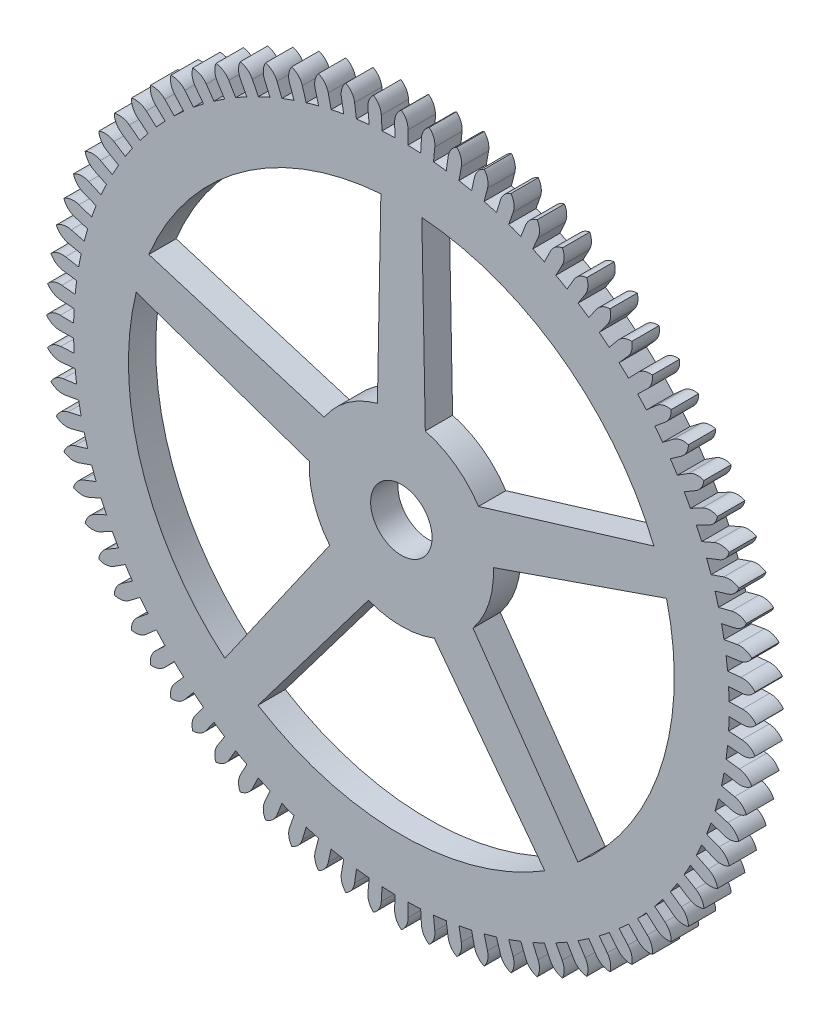
SolidWorks part; units mm, degrees
material "Brass"
ref_plane "Front Plane" through (0, 0, 0) normal (0, 0, 1) x (1, 0, 0)
ref_plane "Top Plane" through (0, 0, 0) normal (0, 1, 0) x (1, 0, 0)
ref_plane "Right Plane" through (0, 0, 0) normal (1, 0, 0) x (0, 0, -1)
sketch "Sketch1" plane through (0, 0, 0) normal (0, 0, 1) x (1, 0, 0)
  line L0 (0, 0) -> (0, 11.4577) construction
  line L1 (-0.1886, 9.6054) -> (-0.1963, 9.9981)
  line L2 (0.1886, 9.6054) -> (0.1963, 9.9981)
  line L3 (0.9417, 9.561) -> (0.9802, 9.9518)
  line L4 (0.5656, 9.5906) -> (0.5887, 9.9827)
  line L5 (1.6889, 9.4577) -> (1.758, 9.8443)
  line L6 (1.3163, 9.5167) -> (1.3701, 9.9057)
  line L7 (2.4258, 9.296) -> (2.5249, 9.676)
  line L8 (2.0589, 9.3841) -> (2.1431, 9.7677)
  line L9 (3.1476, 9.077) -> (3.2763, 9.4481)
  line L10 (2.7888, 9.1936) -> (2.9028, 9.5694)
  line L11 (3.8501, 8.8021) -> (4.0075, 9.1619)
  line L12 (3.5016, 8.9465) -> (3.6447, 9.3122)
  line L13 (4.5289, 8.4729) -> (4.714, 8.8192)
  line L14 (4.1927, 8.6442) -> (4.3641, 8.9975)
  line L15 (5.1797, 8.0914) -> (5.3914, 8.4222)
  line L16 (4.858, 8.2885) -> (5.0566, 8.6273)
  line L17 (5.7985, 7.6601) -> (6.0356, 7.9732)
  line L18 (5.4933, 7.8818) -> (5.7179, 8.204)
  line L19 (6.3817, 7.1815) -> (6.6425, 7.4751)
  line L20 (6.0948, 7.4265) -> (6.3439, 7.7301)
  line L21 (6.9255, 6.6587) -> (7.2085, 6.9309)
  line L22 (6.6587, 6.9255) -> (6.9309, 7.2085)
  line L23 (7.4265, 6.0948) -> (7.7301, 6.3439)
  line L24 (7.1815, 6.3817) -> (7.4751, 6.6425)
  line L25 (7.8818, 5.4933) -> (8.204, 5.7179)
  line L26 (7.6601, 5.7985) -> (7.9732, 6.0356)
  line L27 (8.2885, 4.858) -> (8.6273, 5.0566)
  line L28 (8.0914, 5.1797) -> (8.4222, 5.3914)
  line L29 (8.6442, 4.1927) -> (8.9975, 4.3641)
  line L30 (8.4729, 4.5289) -> (8.8192, 4.714)
  line L31 (8.9465, 3.5016) -> (9.3122, 3.6447)
  line L32 (8.8021, 3.8501) -> (9.1619, 4.0075)
  line L33 (9.1936, 2.7888) -> (9.5694, 2.9028)
  line L34 (9.077, 3.1476) -> (9.4481, 3.2763)
  line L35 (9.3841, 2.0589) -> (9.7677, 2.1431)
  line L36 (9.296, 2.4258) -> (9.676, 2.5249)
  line L37 (9.5167, 1.3163) -> (9.9057, 1.3701)
  line L38 (9.4577, 1.6889) -> (9.8443, 1.758)
  line L39 (9.5906, 0.5656) -> (9.9827, 0.5887)
  line L40 (9.561, 0.9417) -> (9.9518, 0.9802)
  line L41 (9.6054, -0.1886) -> (9.9981, -0.1963)
  line L42 (9.6054, 0.1886) -> (9.9981, 0.1963)
  line L43 (9.561, -0.9417) -> (9.9518, -0.9802)
  line L44 (9.5906, -0.5656) -> (9.9827, -0.5887)
  line L45 (9.4577, -1.6889) -> (9.8443, -1.758)
  line L46 (9.5167, -1.3163) -> (9.9057, -1.3701)
  line L47 (9.296, -2.4258) -> (9.676, -2.5249)
  line L48 (9.3841, -2.0589) -> (9.7677, -2.1431)
  line L49 (9.077, -3.1476) -> (9.4481, -3.2763)
  line L50 (9.1936, -2.7888) -> (9.5694, -2.9028)
  line L51 (8.8021, -3.8501) -> (9.1619, -4.0075)
  line L52 (8.9465, -3.5016) -> (9.3122, -3.6447)
  line L53 (8.4729, -4.5289) -> (8.8192, -4.714)
  line L54 (8.6442, -4.1927) -> (8.9975, -4.3641)
  line L55 (8.0914, -5.1797) -> (8.4222, -5.3914)
  line L56 (8.2885, -4.858) -> (8.6273, -5.0566)
  line L57 (7.6601, -5.7985) -> (7.9732, -6.0356)
  line L58 (7.8818, -5.4933) -> (8.204, -5.7179)
  line L59 (7.1815, -6.3817) -> (7.4751, -6.6425)
  line L60 (7.4265, -6.0948) -> (7.7301, -6.3439)
  line L61 (6.6587, -6.9255) -> (6.9309, -7.2085)
  line L62 (6.9255, -6.6587) -> (7.2085, -6.9309)
  line L63 (6.0948, -7.4265) -> (6.3439, -7.7301)
  line L64 (6.3817, -7.1815) -> (6.6425, -7.4751)
  line L65 (5.4933, -7.8818) -> (5.7179, -8.204)
  line L66 (5.7985, -7.6601) -> (6.0356, -7.9732)
  line L67 (4.858, -8.2885) -> (5.0566, -8.6273)
  line L68 (5.1797, -8.0914) -> (5.3914, -8.4222)
  line L69 (4.1927, -8.6442) -> (4.3641, -8.9975)
  line L70 (4.5289, -8.4729) -> (4.714, -8.8192)
  line L71 (3.5016, -8.9465) -> (3.6447, -9.3122)
  line L72 (3.8501, -8.8021) -> (4.0075, -9.1619)
  line L73 (2.7888, -9.1936) -> (2.9028, -9.5694)
  line L74 (3.1476, -9.077) -> (3.2763, -9.4481)
  line L75 (2.0589, -9.3841) -> (2.1431, -9.7677)
  line L76 (2.4258, -9.296) -> (2.5249, -9.676)
  line L77 (1.3163, -9.5167) -> (1.3701, -9.9057)
  line L78 (1.6889, -9.4577) -> (1.758, -9.8443)
  line L79 (0.5656, -9.5906) -> (0.5887, -9.9827)
  line L80 (0.9417, -9.561) -> (0.9802, -9.9518)
  line L81 (-0.1886, -9.6054) -> (-0.1963, -9.9981)
  line L82 (0.1886, -9.6054) -> (0.1963, -9.9981)
  line L83 (-0.9417, -9.561) -> (-0.9802, -9.9518)
  line L84 (-0.5656, -9.5906) -> (-0.5887, -9.9827)
  line L85 (-1.6889, -9.4577) -> (-1.758, -9.8443)
  line L86 (-1.3163, -9.5167) -> (-1.3701, -9.9057)
  line L87 (-2.4258, -9.296) -> (-2.5249, -9.676)
  line L88 (-2.0589, -9.3841) -> (-2.1431, -9.7677)
  line L89 (-3.1476, -9.077) -> (-3.2763, -9.4481)
  line L90 (-2.7888, -9.1936) -> (-2.9028, -9.5694)
  line L91 (-3.8501, -8.8021) -> (-4.0075, -9.1619)
  line L92 (-3.5016, -8.9465) -> (-3.6447, -9.3122)
  line L93 (-4.5289, -8.4729) -> (-4.714, -8.8192)
  line L94 (-4.1927, -8.6442) -> (-4.3641, -8.9975)
  line L95 (-5.1797, -8.0914) -> (-5.3914, -8.4222)
  line L96 (-4.858, -8.2885) -> (-5.0566, -8.6273)
  line L97 (-5.7985, -7.6601) -> (-6.0356, -7.9732)
  line L98 (-5.4933, -7.8818) -> (-5.7179, -8.204)
  line L99 (-6.3817, -7.1815) -> (-6.6425, -7.4751)
  line L100 (-6.0948, -7.4265) -> (-6.3439, -7.7301)
  line L101 (-6.9255, -6.6587) -> (-7.2085, -6.9309)
  line L102 (-6.6587, -6.9255) -> (-6.9309, -7.2085)
  line L103 (-7.4265, -6.0948) -> (-7.7301, -6.3439)
  line L104 (-7.1815, -6.3817) -> (-7.4751, -6.6425)
  line L105 (-7.8818, -5.4933) -> (-8.204, -5.7179)
  line L106 (-7.6601, -5.7985) -> (-7.9732, -6.0356)
  line L107 (-8.2885, -4.858) -> (-8.6273, -5.0566)
  line L108 (-8.0914, -5.1797) -> (-8.4222, -5.3914)
  line L109 (-8.6442, -4.1927) -> (-8.9975, -4.3641)
  line L110 (-8.4729, -4.5289) -> (-8.8192, -4.714)
  line L111 (-8.9465, -3.5016) -> (-9.3122, -3.6447)
  line L112 (-8.8021, -3.8501) -> (-9.1619, -4.0075)
  line L113 (-9.1936, -2.7888) -> (-9.5694, -2.9028)
  line L114 (-9.077, -3.1476) -> (-9.4481, -3.2763)
  line L115 (-9.3841, -2.0589) -> (-9.7677, -2.1431)
  line L116 (-9.296, -2.4258) -> (-9.676, -2.5249)
  line L117 (-9.5167, -1.3163) -> (-9.9057, -1.3701)
  line L118 (-9.4577, -1.6889) -> (-9.8443, -1.758)
  line L119 (-9.5906, -0.5656) -> (-9.9827, -0.5887)
  line L120 (-9.561, -0.9417) -> (-9.9518, -0.9802)
  line L121 (-9.6054, 0.1886) -> (-9.9981, 0.1963)
  line L122 (-9.6054, -0.1886) -> (-9.9981, -0.1963)
  line L123 (-9.561, 0.9417) -> (-9.9518, 0.9802)
  line L124 (-9.5906, 0.5656) -> (-9.9827, 0.5887)
  line L125 (-9.4577, 1.6889) -> (-9.8443, 1.758)
  line L126 (-9.5167, 1.3163) -> (-9.9057, 1.3701)
  line L127 (-9.296, 2.4258) -> (-9.676, 2.5249)
  line L128 (-9.3841, 2.0589) -> (-9.7677, 2.1431)
  line L129 (-9.077, 3.1476) -> (-9.4481, 3.2763)
  line L130 (-9.1936, 2.7888) -> (-9.5694, 2.9028)
  line L131 (-8.8021, 3.8501) -> (-9.1619, 4.0075)
  line L132 (-8.9465, 3.5016) -> (-9.3122, 3.6447)
  line L133 (-8.4729, 4.5289) -> (-8.8192, 4.714)
  line L134 (-8.6442, 4.1927) -> (-8.9975, 4.3641)
  line L135 (-8.0914, 5.1797) -> (-8.4222, 5.3914)
  line L136 (-8.2885, 4.858) -> (-8.6273, 5.0566)
  line L137 (-7.6601, 5.7985) -> (-7.9732, 6.0356)
  line L138 (-7.8818, 5.4933) -> (-8.204, 5.7179)
  line L139 (-7.1815, 6.3817) -> (-7.4751, 6.6425)
  line L140 (-7.4265, 6.0948) -> (-7.7301, 6.3439)
  line L141 (-6.6587, 6.9255) -> (-6.9309, 7.2085)
  line L142 (-6.9255, 6.6587) -> (-7.2085, 6.9309)
  line L143 (-6.0948, 7.4265) -> (-6.3439, 7.7301)
  line L144 (-6.3817, 7.1815) -> (-6.6425, 7.4751)
  line L145 (-5.4933, 7.8818) -> (-5.7179, 8.204)
  line L146 (-5.7985, 7.6601) -> (-6.0356, 7.9732)
  line L147 (-4.858, 8.2885) -> (-5.0566, 8.6273)
  line L148 (-5.1797, 8.0914) -> (-5.3914, 8.4222)
  line L149 (-4.1927, 8.6442) -> (-4.3641, 8.9975)
  line L150 (-4.5289, 8.4729) -> (-4.714, 8.8192)
  line L151 (-3.5016, 8.9465) -> (-3.6447, 9.3122)
  line L152 (-3.8501, 8.8021) -> (-4.0075, 9.1619)
  line L153 (-2.7888, 9.1936) -> (-2.9028, 9.5694)
  line L154 (-3.1476, 9.077) -> (-3.2763, 9.4481)
  line L155 (-2.0589, 9.3841) -> (-2.1431, 9.7677)
  line L156 (-2.4258, 9.296) -> (-2.5249, 9.676)
  line L157 (-1.3163, 9.5167) -> (-1.3701, 9.9057)
  line L158 (-1.6889, 9.4577) -> (-1.758, 9.8443)
  line L159 (-0.5656, 9.5906) -> (-0.5887, 9.9827)
  line L160 (-0.9417, 9.561) -> (-0.9802, 9.9518)
  line L161 (-0.6, 8) -> (-0.7018, 2.6072)
  line L162 (0.6, 8) -> (0.7018, 2.6072)
  line L163 (7.423, 3.0428) -> (2.2628, 1.4731)
  line L164 (7.7939, 1.9015) -> (2.6965, 0.1383)
  line L165 (5.1877, -6.1195) -> (2.1002, -1.6968)
  line L166 (4.2169, -6.8248) -> (0.9648, -2.5218)
  line L167 (-4.2169, -6.8248) -> (-0.9648, -2.5218)
  line L168 (-5.1877, -6.1195) -> (-2.1002, -1.6968)
  line L169 (-7.7939, 1.9015) -> (-2.6965, 0.1383)
  line L170 (-7.423, 3.0428) -> (-2.2628, 1.4731)
  arc A0 (0.5656, 9.5906) -> (0.1886, 9.6054) centre (0, 0) ccw
  arc A1 (-0.1886, 9.6054) -> (-0.5656, 9.5906) centre (0, 0) ccw
  arc A2 (1.3163, 9.5167) -> (0.9417, 9.561) centre (0, 0) ccw
  arc A3 (-0.1963, 9.9981) -> (0, 10.4017) centre (0.2968, 10.0078) cw
  arc A4 (0.1963, 9.9981) -> (0, 10.4017) centre (-0.2968, 10.0078) ccw
  arc A5 (0.5887, 9.9827) -> (0.8161, 10.3696) centre (1.0811, 9.9536) cw
  arc A6 (0.9802, 9.9518) -> (0.8161, 10.3696) centre (0.4893, 10.0002) ccw
  arc A7 (1.3701, 9.9057) -> (1.6272, 10.2736) centre (1.8587, 9.8381) cw
  arc A8 (1.758, 9.8443) -> (1.6272, 10.2736) centre (1.2724, 9.931) ccw
  arc A9 (2.1431, 9.7677) -> (2.4282, 10.1143) centre (2.6249, 9.662) cw
  arc A10 (2.5249, 9.676) -> (2.4282, 10.1143) centre (2.0477, 9.8005) ccw
  arc A11 (2.9028, 9.5694) -> (3.2143, 9.8926) centre (3.3748, 9.4262) cw
  arc A12 (3.2763, 9.4481) -> (3.2143, 9.8926) centre (2.8103, 9.6097) ccw
  arc A13 (3.6447, 9.3122) -> (3.9806, 9.6099) centre (4.104, 9.1324) cw
  arc A14 (4.0075, 9.1619) -> (3.9806, 9.6099) centre (3.5556, 9.3595) ccw
  arc A15 (4.3641, 8.9975) -> (4.7223, 9.268) centre (4.8079, 8.7822) cw
  arc A16 (4.714, 8.8192) -> (4.7223, 9.268) centre (4.279, 9.0517) ccw
  arc A17 (5.0566, 8.6273) -> (5.4349, 8.8689) centre (5.4821, 8.3779) cw
  arc A18 (5.3914, 8.4222) -> (5.4349, 8.8689) centre (4.976, 8.6881) ccw
  arc A19 (5.7179, 8.204) -> (6.114, 8.4152) centre (6.1225, 7.922) cw
  arc A20 (6.0356, 7.9732) -> (6.114, 8.4152) centre (5.6423, 8.2709) ccw
  arc A21 (6.3439, 7.7301) -> (6.7554, 7.9095) centre (6.7252, 7.4172) cw
  arc A22 (6.6425, 7.4751) -> (6.7554, 7.9095) centre (6.2738, 7.8027) ccw
  arc A23 (6.9309, 7.2085) -> (7.3551, 7.3551) centre (7.2864, 6.8667) cw
  arc A24 (7.2085, 6.9309) -> (7.3551, 7.3551) centre (6.8667, 7.2864) ccw
  arc A25 (7.4751, 6.6425) -> (7.9095, 6.7554) centre (7.8027, 6.2738) cw
  arc A26 (7.7301, 6.3439) -> (7.9095, 6.7554) centre (7.4172, 6.7252) ccw
  arc A27 (7.9732, 6.0356) -> (8.4152, 6.114) centre (8.2709, 5.6423) cw
  arc A28 (8.204, 5.7179) -> (8.4152, 6.114) centre (7.922, 6.1225) ccw
  arc A29 (8.4222, 5.3914) -> (8.8689, 5.4349) centre (8.6881, 4.976) cw
  arc A30 (8.6273, 5.0566) -> (8.8689, 5.4349) centre (8.3779, 5.4821) ccw
  arc A31 (8.8192, 4.714) -> (9.268, 4.7223) centre (9.0517, 4.279) cw
  arc A32 (8.9975, 4.3641) -> (9.268, 4.7223) centre (8.7822, 4.8079) ccw
  arc A33 (9.1619, 4.0075) -> (9.6099, 3.9806) centre (9.3595, 3.5556) cw
  arc A34 (9.3122, 3.6447) -> (9.6099, 3.9806) centre (9.1324, 4.104) ccw
  arc A35 (9.4481, 3.2763) -> (9.8926, 3.2143) centre (9.6097, 2.8103) cw
  arc A36 (9.5694, 2.9028) -> (9.8926, 3.2143) centre (9.4262, 3.3748) ccw
  arc A37 (9.676, 2.5249) -> (10.1143, 2.4282) centre (9.8005, 2.0477) cw
  arc A38 (9.7677, 2.1431) -> (10.1143, 2.4282) centre (9.662, 2.6249) ccw
  arc A39 (9.8443, 1.758) -> (10.2736, 1.6272) centre (9.931, 1.2724) cw
  arc A40 (9.9057, 1.3701) -> (10.2736, 1.6272) centre (9.8381, 1.8587) ccw
  arc A41 (9.9518, 0.9802) -> (10.3696, 0.8161) centre (10.0002, 0.4893) cw
  arc A42 (9.9827, 0.5887) -> (10.3696, 0.8161) centre (9.9536, 1.0811) ccw
  arc A43 (9.9981, 0.1963) -> (10.4017, 0) centre (10.0078, -0.2968) cw
  arc A44 (9.9981, -0.1963) -> (10.4017, 0) centre (10.0078, 0.2968) ccw
  arc A45 (9.9827, -0.5887) -> (10.3696, -0.8161) centre (9.9536, -1.0811) cw
  arc A46 (9.9518, -0.9802) -> (10.3696, -0.8161) centre (10.0002, -0.4893) ccw
  arc A47 (9.9057, -1.3701) -> (10.2736, -1.6272) centre (9.8381, -1.8587) cw
  arc A48 (9.8443, -1.758) -> (10.2736, -1.6272) centre (9.931, -1.2724) ccw
  arc A49 (9.7677, -2.1431) -> (10.1143, -2.4282) centre (9.662, -2.6249) cw
  arc A50 (9.676, -2.5249) -> (10.1143, -2.4282) centre (9.8005, -2.0477) ccw
  arc A51 (9.5694, -2.9028) -> (9.8926, -3.2143) centre (9.4262, -3.3748) cw
  arc A52 (9.4481, -3.2763) -> (9.8926, -3.2143) centre (9.6097, -2.8103) ccw
  arc A53 (9.3122, -3.6447) -> (9.6099, -3.9806) centre (9.1324, -4.104) cw
  arc A54 (9.1619, -4.0075) -> (9.6099, -3.9806) centre (9.3595, -3.5556) ccw
  arc A55 (8.9975, -4.3641) -> (9.268, -4.7223) centre (8.7822, -4.8079) cw
  arc A56 (8.8192, -4.714) -> (9.268, -4.7223) centre (9.0517, -4.279) ccw
  arc A57 (8.6273, -5.0566) -> (8.8689, -5.4349) centre (8.3779, -5.4821) cw
  arc A58 (8.4222, -5.3914) -> (8.8689, -5.4349) centre (8.6881, -4.976) ccw
  arc A59 (8.204, -5.7179) -> (8.4152, -6.114) centre (7.922, -6.1225) cw
  arc A60 (7.9732, -6.0356) -> (8.4152, -6.114) centre (8.2709, -5.6423) ccw
  arc A61 (7.7301, -6.3439) -> (7.9095, -6.7554) centre (7.4172, -6.7252) cw
  arc A62 (7.4751, -6.6425) -> (7.9095, -6.7554) centre (7.8027, -6.2738) ccw
  arc A63 (7.2085, -6.9309) -> (7.3551, -7.3551) centre (6.8667, -7.2864) cw
  arc A64 (6.9309, -7.2085) -> (7.3551, -7.3551) centre (7.2864, -6.8667) ccw
  arc A65 (6.6425, -7.4751) -> (6.7554, -7.9095) centre (6.2738, -7.8027) cw
  arc A66 (6.3439, -7.7301) -> (6.7554, -7.9095) centre (6.7252, -7.4172) ccw
  arc A67 (6.0356, -7.9732) -> (6.114, -8.4152) centre (5.6423, -8.2709) cw
  arc A68 (5.7179, -8.204) -> (6.114, -8.4152) centre (6.1225, -7.922) ccw
  arc A69 (5.3914, -8.4222) -> (5.4349, -8.8689) centre (4.976, -8.6881) cw
  arc A70 (5.0566, -8.6273) -> (5.4349, -8.8689) centre (5.4821, -8.3779) ccw
  arc A71 (4.714, -8.8192) -> (4.7223, -9.268) centre (4.279, -9.0517) cw
  arc A72 (4.3641, -8.9975) -> (4.7223, -9.268) centre (4.8079, -8.7822) ccw
  arc A73 (4.0075, -9.1619) -> (3.9806, -9.6099) centre (3.5556, -9.3595) cw
  arc A74 (3.6447, -9.3122) -> (3.9806, -9.6099) centre (4.104, -9.1324) ccw
  arc A75 (3.2763, -9.4481) -> (3.2143, -9.8926) centre (2.8103, -9.6097) cw
  arc A76 (2.9028, -9.5694) -> (3.2143, -9.8926) centre (3.3748, -9.4262) ccw
  arc A77 (2.5249, -9.676) -> (2.4282, -10.1143) centre (2.0477, -9.8005) cw
  arc A78 (2.1431, -9.7677) -> (2.4282, -10.1143) centre (2.6249, -9.662) ccw
  arc A79 (1.758, -9.8443) -> (1.6272, -10.2736) centre (1.2724, -9.931) cw
  arc A80 (1.3701, -9.9057) -> (1.6272, -10.2736) centre (1.8587, -9.8381) ccw
  arc A81 (0.9802, -9.9518) -> (0.8161, -10.3696) centre (0.4893, -10.0002) cw
  arc A82 (0.5887, -9.9827) -> (0.8161, -10.3696) centre (1.0811, -9.9536) ccw
  arc A83 (0.1963, -9.9981) -> (0, -10.4017) centre (-0.2968, -10.0078) cw
  arc A84 (-0.1963, -9.9981) -> (0, -10.4017) centre (0.2968, -10.0078) ccw
  arc A85 (-0.5887, -9.9827) -> (-0.8161, -10.3696) centre (-1.0811, -9.9536) cw
  arc A86 (-0.9802, -9.9518) -> (-0.8161, -10.3696) centre (-0.4893, -10.0002) ccw
  arc A87 (-1.3701, -9.9057) -> (-1.6272, -10.2736) centre (-1.8587, -9.8381) cw
  arc A88 (-1.758, -9.8443) -> (-1.6272, -10.2736) centre (-1.2724, -9.931) ccw
  arc A89 (-2.1431, -9.7677) -> (-2.4282, -10.1143) centre (-2.6249, -9.662) cw
  arc A90 (-2.5249, -9.676) -> (-2.4282, -10.1143) centre (-2.0477, -9.8005) ccw
  arc A91 (-2.9028, -9.5694) -> (-3.2143, -9.8926) centre (-3.3748, -9.4262) cw
  arc A92 (-3.2763, -9.4481) -> (-3.2143, -9.8926) centre (-2.8103, -9.6097) ccw
  arc A93 (-3.6447, -9.3122) -> (-3.9806, -9.6099) centre (-4.104, -9.1324) cw
  arc A94 (-4.0075, -9.1619) -> (-3.9806, -9.6099) centre (-3.5556, -9.3595) ccw
  arc A95 (-4.3641, -8.9975) -> (-4.7223, -9.268) centre (-4.8079, -8.7822) cw
  arc A96 (-4.714, -8.8192) -> (-4.7223, -9.268) centre (-4.279, -9.0517) ccw
  arc A97 (-5.0566, -8.6273) -> (-5.4349, -8.8689) centre (-5.4821, -8.3779) cw
  arc A98 (-5.3914, -8.4222) -> (-5.4349, -8.8689) centre (-4.976, -8.6881) ccw
  arc A99 (-5.7179, -8.204) -> (-6.114, -8.4152) centre (-6.1225, -7.922) cw
  arc A100 (-6.0356, -7.9732) -> (-6.114, -8.4152) centre (-5.6423, -8.2709) ccw
  arc A101 (-6.3439, -7.7301) -> (-6.7554, -7.9095) centre (-6.7252, -7.4172) cw
  arc A102 (-6.6425, -7.4751) -> (-6.7554, -7.9095) centre (-6.2738, -7.8027) ccw
  arc A103 (-6.9309, -7.2085) -> (-7.3551, -7.3551) centre (-7.2864, -6.8667) cw
  arc A104 (-7.2085, -6.9309) -> (-7.3551, -7.3551) centre (-6.8667, -7.2864) ccw
  arc A105 (-7.4751, -6.6425) -> (-7.9095, -6.7554) centre (-7.8027, -6.2738) cw
  arc A106 (-7.7301, -6.3439) -> (-7.9095, -6.7554) centre (-7.4172, -6.7252) ccw
  arc A107 (-7.9732, -6.0356) -> (-8.4152, -6.114) centre (-8.2709, -5.6423) cw
  arc A108 (-8.204, -5.7179) -> (-8.4152, -6.114) centre (-7.922, -6.1225) ccw
  arc A109 (-8.4222, -5.3914) -> (-8.8689, -5.4349) centre (-8.6881, -4.976) cw
  arc A110 (-8.6273, -5.0566) -> (-8.8689, -5.4349) centre (-8.3779, -5.4821) ccw
  arc A111 (-8.8192, -4.714) -> (-9.268, -4.7223) centre (-9.0517, -4.279) cw
  arc A112 (-8.9975, -4.3641) -> (-9.268, -4.7223) centre (-8.7822, -4.8079) ccw
  arc A113 (-9.1619, -4.0075) -> (-9.6099, -3.9806) centre (-9.3595, -3.5556) cw
  arc A114 (-9.3122, -3.6447) -> (-9.6099, -3.9806) centre (-9.1324, -4.104) ccw
  arc A115 (-9.4481, -3.2763) -> (-9.8926, -3.2143) centre (-9.6097, -2.8103) cw
  arc A116 (-9.5694, -2.9028) -> (-9.8926, -3.2143) centre (-9.4262, -3.3748) ccw
  arc A117 (-9.676, -2.5249) -> (-10.1143, -2.4282) centre (-9.8005, -2.0477) cw
  arc A118 (-9.7677, -2.1431) -> (-10.1143, -2.4282) centre (-9.662, -2.6249) ccw
  arc A119 (-9.8443, -1.758) -> (-10.2736, -1.6272) centre (-9.931, -1.2724) cw
  arc A120 (-9.9057, -1.3701) -> (-10.2736, -1.6272) centre (-9.8381, -1.8587) ccw
  arc A121 (-9.9518, -0.9802) -> (-10.3696, -0.8161) centre (-10.0002, -0.4893) cw
  arc A122 (-9.9827, -0.5887) -> (-10.3696, -0.8161) centre (-9.9536, -1.0811) ccw
  arc A123 (-9.9981, -0.1963) -> (-10.4017, 0) centre (-10.0078, 0.2968) cw
  arc A124 (-9.9981, 0.1963) -> (-10.4017, 0) centre (-10.0078, -0.2968) ccw
  arc A125 (-9.9827, 0.5887) -> (-10.3696, 0.8161) centre (-9.9536, 1.0811) cw
  arc A126 (-9.9518, 0.9802) -> (-10.3696, 0.8161) centre (-10.0002, 0.4893) ccw
  arc A127 (-9.9057, 1.3701) -> (-10.2736, 1.6272) centre (-9.8381, 1.8587) cw
  arc A128 (-9.8443, 1.758) -> (-10.2736, 1.6272) centre (-9.931, 1.2724) ccw
  arc A129 (-9.7677, 2.1431) -> (-10.1143, 2.4282) centre (-9.662, 2.6249) cw
  arc A130 (-9.676, 2.5249) -> (-10.1143, 2.4282) centre (-9.8005, 2.0477) ccw
  arc A131 (-9.5694, 2.9028) -> (-9.8926, 3.2143) centre (-9.4262, 3.3748) cw
  arc A132 (-9.4481, 3.2763) -> (-9.8926, 3.2143) centre (-9.6097, 2.8103) ccw
  arc A133 (-9.3122, 3.6447) -> (-9.6099, 3.9806) centre (-9.1324, 4.104) cw
  arc A134 (-9.1619, 4.0075) -> (-9.6099, 3.9806) centre (-9.3595, 3.5556) ccw
  arc A135 (-8.9975, 4.3641) -> (-9.268, 4.7223) centre (-8.7822, 4.8079) cw
  arc A136 (-8.8192, 4.714) -> (-9.268, 4.7223) centre (-9.0517, 4.279) ccw
  arc A137 (-8.6273, 5.0566) -> (-8.8689, 5.4349) centre (-8.3779, 5.4821) cw
  arc A138 (-8.4222, 5.3914) -> (-8.8689, 5.4349) centre (-8.6881, 4.976) ccw
  arc A139 (-8.204, 5.7179) -> (-8.4152, 6.114) centre (-7.922, 6.1225) cw
  arc A140 (-7.9732, 6.0356) -> (-8.4152, 6.114) centre (-8.2709, 5.6423) ccw
  arc A141 (-7.7301, 6.3439) -> (-7.9095, 6.7554) centre (-7.4172, 6.7252) cw
  arc A142 (-7.4751, 6.6425) -> (-7.9095, 6.7554) centre (-7.8027, 6.2738) ccw
  arc A143 (-7.2085, 6.9309) -> (-7.3551, 7.3551) centre (-6.8667, 7.2864) cw
  arc A144 (-6.9309, 7.2085) -> (-7.3551, 7.3551) centre (-7.2864, 6.8667) ccw
  arc A145 (-6.6425, 7.4751) -> (-6.7554, 7.9095) centre (-6.2738, 7.8027) cw
  arc A146 (-6.3439, 7.7301) -> (-6.7554, 7.9095) centre (-6.7252, 7.4172) ccw
  arc A147 (-6.0356, 7.9732) -> (-6.114, 8.4152) centre (-5.6423, 8.2709) cw
  arc A148 (-5.7179, 8.204) -> (-6.114, 8.4152) centre (-6.1225, 7.922) ccw
  arc A149 (-5.3914, 8.4222) -> (-5.4349, 8.8689) centre (-4.976, 8.6881) cw
  arc A150 (-5.0566, 8.6273) -> (-5.4349, 8.8689) centre (-5.4821, 8.3779) ccw
  arc A151 (-4.714, 8.8192) -> (-4.7223, 9.268) centre (-4.279, 9.0517) cw
  arc A152 (-4.3641, 8.9975) -> (-4.7223, 9.268) centre (-4.8079, 8.7822) ccw
  arc A153 (-4.0075, 9.1619) -> (-3.9806, 9.6099) centre (-3.5556, 9.3595) cw
  arc A154 (-3.6447, 9.3122) -> (-3.9806, 9.6099) centre (-4.104, 9.1324) ccw
  arc A155 (-3.2763, 9.4481) -> (-3.2143, 9.8926) centre (-2.8103, 9.6097) cw
  arc A156 (-2.9028, 9.5694) -> (-3.2143, 9.8926) centre (-3.3748, 9.4262) ccw
  arc A157 (-2.5249, 9.676) -> (-2.4282, 10.1143) centre (-2.0477, 9.8005) cw
  arc A158 (-2.1431, 9.7677) -> (-2.4282, 10.1143) centre (-2.6249, 9.662) ccw
  arc A159 (-1.758, 9.8443) -> (-1.6272, 10.2736) centre (-1.2724, 9.931) cw
  arc A160 (-1.3701, 9.9057) -> (-1.6272, 10.2736) centre (-1.8587, 9.8381) ccw
  arc A161 (-0.9802, 9.9518) -> (-0.8161, 10.3696) centre (-0.4893, 10.0002) cw
  arc A162 (-0.5887, 9.9827) -> (-0.8161, 10.3696) centre (-1.0811, 9.9536) ccw
  arc A163 (2.0589, 9.3841) -> (1.6889, 9.4577) centre (0, 0) ccw
  arc A164 (2.7888, 9.1936) -> (2.4258, 9.296) centre (0, 0) ccw
  arc A165 (3.5016, 8.9465) -> (3.1476, 9.077) centre (0, 0) ccw
  arc A166 (4.1927, 8.6442) -> (3.8501, 8.8021) centre (0, 0) ccw
  arc A167 (4.858, 8.2885) -> (4.5289, 8.4729) centre (0, 0) ccw
  arc A168 (5.4933, 7.8818) -> (5.1797, 8.0914) centre (0, 0) ccw
  arc A169 (6.0948, 7.4265) -> (5.7985, 7.6601) centre (0, 0) ccw
  arc A170 (-0.9417, 9.561) -> (-1.3163, 9.5167) centre (0, 0) ccw
  arc A171 (-1.6889, 9.4577) -> (-2.0589, 9.3841) centre (0, 0) ccw
  arc A172 (-2.4258, 9.296) -> (-2.7888, 9.1936) centre (0, 0) ccw
  arc A173 (-3.1476, 9.077) -> (-3.5016, 8.9465) centre (0, 0) ccw
  arc A174 (-3.8501, 8.8021) -> (-4.1927, 8.6442) centre (0, 0) ccw
  arc A175 (-4.5289, 8.4729) -> (-4.858, 8.2885) centre (0, 0) ccw
  arc A176 (-5.1797, 8.0914) -> (-5.4933, 7.8818) centre (0, 0) ccw
  arc A177 (-5.7985, 7.6601) -> (-6.0948, 7.4265) centre (0, 0) ccw
  arc A178 (-6.3817, 7.1815) -> (-6.6587, 6.9255) centre (0, 0) ccw
  arc A179 (-6.9255, 6.6587) -> (-7.1815, 6.3817) centre (0, 0) ccw
  arc A180 (-7.4265, 6.0948) -> (-7.6601, 5.7985) centre (0, 0) ccw
  arc A181 (-7.8818, 5.4933) -> (-8.0914, 5.1797) centre (0, 0) ccw
  arc A182 (-8.2885, 4.858) -> (-8.4729, 4.5289) centre (0, 0) ccw
  arc A183 (-8.6442, 4.1927) -> (-8.8021, 3.8501) centre (0, 0) ccw
  arc A184 (-8.9465, 3.5016) -> (-9.077, 3.1476) centre (0, 0) ccw
  arc A185 (-9.1936, 2.7888) -> (-9.296, 2.4258) centre (0, 0) ccw
  arc A186 (-9.3841, 2.0589) -> (-9.4577, 1.6889) centre (0, 0) ccw
  arc A187 (-9.5167, 1.3163) -> (-9.561, 0.9417) centre (0, 0) ccw
  arc A188 (-9.5906, 0.5656) -> (-9.6054, 0.1886) centre (0, 0) ccw
  arc A189 (-9.6054, -0.1886) -> (-9.5906, -0.5656) centre (0, 0) ccw
  arc A190 (-9.561, -0.9417) -> (-9.5167, -1.3163) centre (0, 0) ccw
  arc A191 (-9.4577, -1.6889) -> (-9.3841, -2.0589) centre (0, 0) ccw
  arc A192 (-9.296, -2.4258) -> (-9.1936, -2.7888) centre (0, 0) ccw
  arc A193 (-9.077, -3.1476) -> (-8.9465, -3.5016) centre (0, 0) ccw
  arc A194 (-8.8021, -3.8501) -> (-8.6442, -4.1927) centre (0, 0) ccw
  arc A195 (-8.4729, -4.5289) -> (-8.2885, -4.858) centre (0, 0) ccw
  arc A196 (-8.0914, -5.1797) -> (-7.8818, -5.4933) centre (0, 0) ccw
  arc A197 (-7.6601, -5.7985) -> (-7.4265, -6.0948) centre (0, 0) ccw
  arc A198 (-7.1815, -6.3817) -> (-6.9255, -6.6587) centre (0, 0) ccw
  arc A199 (-6.6587, -6.9255) -> (-6.3817, -7.1815) centre (0, 0) ccw
  arc A200 (-6.0948, -7.4265) -> (-5.7985, -7.6601) centre (0, 0) ccw
  arc A201 (-5.4933, -7.8818) -> (-5.1797, -8.0914) centre (0, 0) ccw
  arc A202 (-4.858, -8.2885) -> (-4.5289, -8.4729) centre (0, 0) ccw
  arc A203 (-4.1927, -8.6442) -> (-3.8501, -8.8021) centre (0, 0) ccw
  arc A204 (-3.5016, -8.9465) -> (-3.1476, -9.077) centre (0, 0) ccw
  arc A205 (-2.7888, -9.1936) -> (-2.4258, -9.296) centre (0, 0) ccw
  arc A206 (-2.0589, -9.3841) -> (-1.6889, -9.4577) centre (0, 0) ccw
  arc A207 (-1.3163, -9.5167) -> (-0.9417, -9.561) centre (0, 0) ccw
  arc A208 (-0.5656, -9.5906) -> (-0.1886, -9.6054) centre (0, 0) ccw
  arc A209 (0.1886, -9.6054) -> (0.5656, -9.5906) centre (0, 0) ccw
  arc A210 (0.9417, -9.561) -> (1.3163, -9.5167) centre (0, 0) ccw
  arc A211 (1.6889, -9.4577) -> (2.0589, -9.3841) centre (0, 0) ccw
  arc A212 (2.4258, -9.296) -> (2.7888, -9.1936) centre (0, 0) ccw
  arc A213 (3.1476, -9.077) -> (3.5016, -8.9465) centre (0, 0) ccw
  arc A214 (3.8501, -8.8021) -> (4.1927, -8.6442) centre (0, 0) ccw
  arc A215 (4.5289, -8.4729) -> (4.858, -8.2885) centre (0, 0) ccw
  arc A216 (5.1797, -8.0914) -> (5.4933, -7.8818) centre (0, 0) ccw
  arc A217 (5.7985, -7.6601) -> (6.0948, -7.4265) centre (0, 0) ccw
  arc A218 (6.3817, -7.1815) -> (6.6587, -6.9255) centre (0, 0) ccw
  arc A219 (6.9255, -6.6587) -> (7.1815, -6.3817) centre (0, 0) ccw
  arc A220 (7.4265, -6.0948) -> (7.6601, -5.7985) centre (0, 0) ccw
  arc A221 (7.8818, -5.4933) -> (8.0914, -5.1797) centre (0, 0) ccw
  arc A222 (8.2885, -4.858) -> (8.4729, -4.5289) centre (0, 0) ccw
  arc A223 (8.6442, -4.1927) -> (8.8021, -3.8501) centre (0, 0) ccw
  arc A224 (8.9465, -3.5016) -> (9.077, -3.1476) centre (0, 0) ccw
  arc A225 (9.1936, -2.7888) -> (9.296, -2.4258) centre (0, 0) ccw
  arc A226 (9.3841, -2.0589) -> (9.4577, -1.6889) centre (0, 0) ccw
  arc A227 (9.5167, -1.3163) -> (9.561, -0.9417) centre (0, 0) ccw
  arc A228 (9.5906, -0.5656) -> (9.6054, -0.1886) centre (0, 0) ccw
  arc A229 (9.6054, 0.1886) -> (9.5906, 0.5656) centre (0, 0) ccw
  arc A230 (9.561, 0.9417) -> (9.5167, 1.3163) centre (0, 0) ccw
  arc A231 (9.4577, 1.6889) -> (9.3841, 2.0589) centre (0, 0) ccw
  arc A232 (9.296, 2.4258) -> (9.1936, 2.7888) centre (0, 0) ccw
  arc A233 (9.077, 3.1476) -> (8.9465, 3.5016) centre (0, 0) ccw
  arc A234 (8.8021, 3.8501) -> (8.6442, 4.1927) centre (0, 0) ccw
  arc A235 (8.4729, 4.5289) -> (8.2885, 4.858) centre (0, 0) ccw
  arc A236 (8.0914, 5.1797) -> (7.8818, 5.4933) centre (0, 0) ccw
  arc A237 (7.6601, 5.7985) -> (7.4265, 6.0948) centre (0, 0) ccw
  arc A238 (7.1815, 6.3817) -> (6.9255, 6.6587) centre (0, 0) ccw
  arc A239 (6.6587, 6.9255) -> (6.3817, 7.1815) centre (0, 0) ccw
  circle A240 centre (0, 0) radius 0.9
  circle A241 centre (0, 0) radius 2.7
  circle A242 centre (0, 0) radius 8
  point P568 (0, 0)
  point P589 (0, 0)
  dimension "D1" = 1.8
  dimension "D2" = 19.2146
  dimension "D3" = 5.4
  dimension "D4" = 80
  dimension "D5" = 16
  dimension "D6" = 5
extrude "Boss-Extrude1" add sketch "Sketch1" along normal blind 0.8 contours A242 A3 L1 A1 L159 A162 A161 L160 A170 L157 A160 A159 L158 A171 L155 A158 A157 L156 A172 L153 A156 A155 L154 A173 L151 A154 | L0 A241 L162 A242 | A241 L0 A242 L161 | L170 A242 L169 A241 | L168 A242 L167 A241 | A240 A241 | L164 A242 L163 A241 | L166 A242 L165 A241 region at (0.3439, 2.601, 0) region at (-0.3267, 5.2623, 0) region at (0.3267, 5.2623, 0) region at (-0.1178, 10.0948, 0) region at (5.0048, 1.6262, 0) region at (-5.0048, 1.6262, 0) region at (-3.0931, -4.2573, 0) region at (3.0931, -4.2573, 0)
